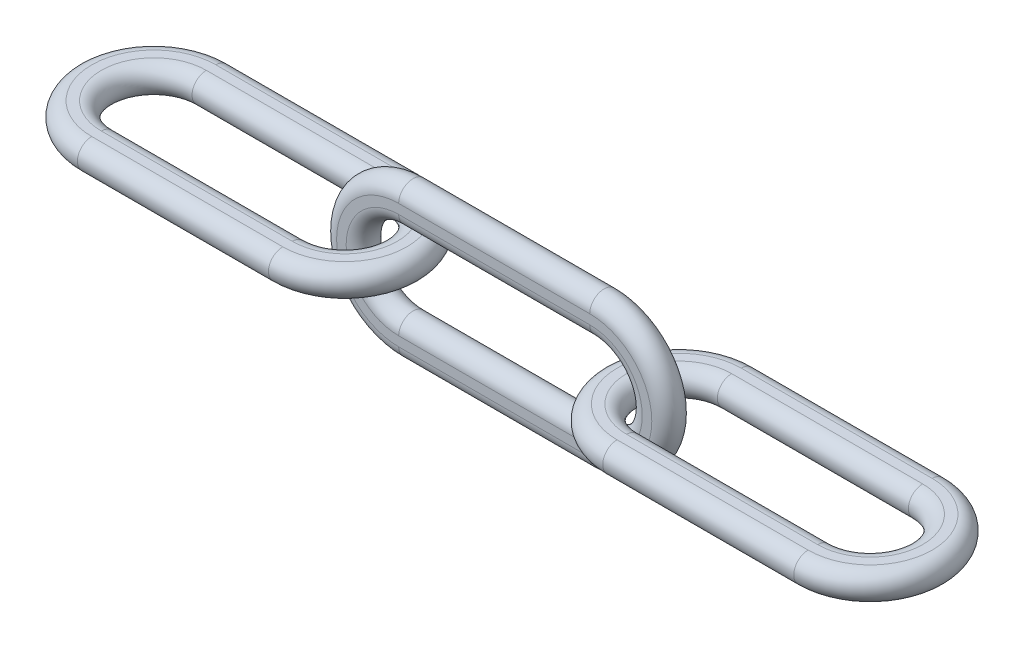
SolidWorks part; units mm, degrees
ref_plane "Piano frontale" through (0, 0, 0) normal (0, 0, 1) x (1, 0, 0)
ref_plane "Piano superiore" through (0, 0, 0) normal (0, 1, 0) x (1, 0, 0)
ref_plane "Piano destro" through (0, 0, 0) normal (1, 0, 0) x (0, 0, -1)
sketch "Schizzo1" plane through (0, 0, 0) normal (0, 1, 0) x (1, 0, 0)
  line L0 (-7.0609, 0) -> (2.9391, 0) construction
  line L1 (-7.0609, 4) -> (2.9391, 4)
  line L2 (-7.0609, -4) -> (2.9391, -4)
  line L3 (-7.0609, 2) -> (2.9391, 2)
  line L4 (-7.0609, -2) -> (2.9391, -2)
  arc A0 (-7.0609, 4) -> (-7.0609, -4) centre (-7.0609, 0) ccw
  arc A1 (2.9391, -4) -> (2.9391, 4) centre (2.9391, 0) ccw
  arc A2 (2.9391, -2) -> (2.9391, 2) centre (2.9391, 0) ccw
  arc A3 (-7.0609, 2) -> (-7.0609, -2) centre (-7.0609, 0) ccw
  point P3 (-2.0609, 0)
  dimension "D2" = 4
  dimension "D3" = 2
  dimension "D1" = 10
extrude "Estrusione-Estrusione1" add sketch "Schizzo1" along normal blind 1.5
fillet "Raccordo9" 2 edges at (-2.0609, 0, -4) (-2.0609, 1.5, -4) type full round first side face at (-2.0609, 0, 0) second side face at (-2.0609, 1.5, 0) middle face at (-2.0609, 0.75, -4)
fillet "Raccordo13" 2 edges at (-2.0609, 1.5, -2) (-2.0609, 0, -2) type full round first side face at (-2.0609, 1.5, 0) second side face at (-2.0609, 0, 0) middle face at (-2.0609, 0.75, -2)
sketch "Schizzo2" plane through (0, 0, 0) normal (0, 1, 0) x (1, 0, 0)
  line L0 (-2.5843, 8.9767) -> (-2.5843, -11.7532) construction
  line L1 (-16.4583, 0) -> (14.3127, 0) construction
sketch "Schizzo3" plane through (0, 0, 0) normal (0, 0, 1) x (1, 0, 0)
  line L0 (6.5071, 0.75) -> (16.5071, 0.75) construction
  line L1 (6.5071, 4.75) -> (16.5071, 4.75)
  line L2 (6.5071, 2.75) -> (16.5071, 2.75)
  line L3 (6.5071, -1.25) -> (16.5071, -1.25)
  line L4 (6.5071, -3.25) -> (16.5071, -3.25)
  arc A0 (6.5071, 2.75) -> (6.5071, -1.25) centre (6.5071, 0.75) ccw
  arc A1 (16.5071, -1.25) -> (16.5071, 2.75) centre (16.5071, 0.75) ccw
  arc A2 (16.5071, -3.25) -> (16.5071, 4.75) centre (16.5071, 0.75) ccw
  arc A3 (6.5071, 4.75) -> (6.5071, -3.25) centre (6.5071, 0.75) ccw
  point P2 (11.5071, 0.75)
  dimension "D2" = 2
  dimension "D1" = 10
extrude "Estrusione-Estrusione2" add sketch "Schizzo3" along normal mid plane 1.5
fillet "Raccordo16" 2 edges at (11.5071, 4.75, 0.75) (11.5071, 4.75, -0.75) type full round first side face at (11.5071, 0.75, 0.75) second side face at (11.5071, 0.75, -0.75) middle face at (11.5071, 4.75, 0)
fillet "Raccordo17" 2 edges at (11.5071, -1.25, -0.75) (11.5071, -1.25, 0.75) type full round first side face at (11.5071, 0.75, -0.75) second side face at (11.5071, 0.75, 0.75) middle face at (11.5071, -1.25, 0)
pattern_linear "Ripetizione a L2" count 2 spacing 27.5 along (1, 0, 0) of bodies 101
